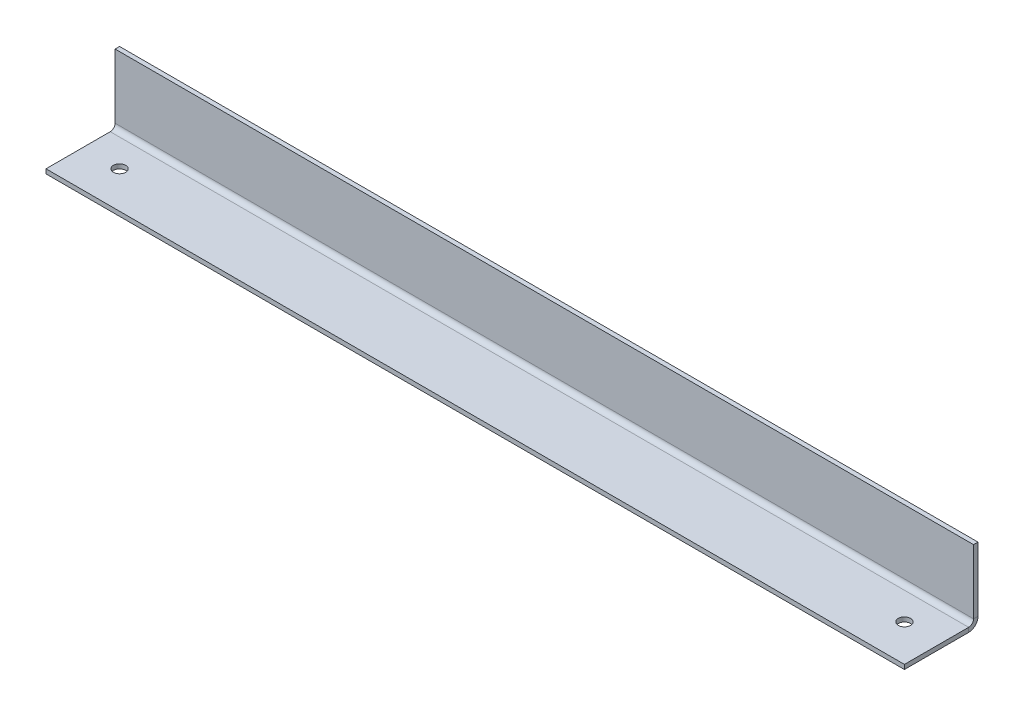
SolidWorks part; units mm, degrees
note: The reader was unsure of these and kept them because the rebuilt part matched: flange length of "Edge-Flange1".
ref_plane "Front Plane" through (0, 0, 0) normal (0, 0, 1) x (1, 0, 0)
ref_plane "Top Plane" through (0, 0, 0) normal (0, 1, 0) x (1, 0, 0)
ref_plane "Right Plane" through (0, 0, 0) normal (1, 0, 0) x (0, 0, -1)
sketch "Sketch1" plane through (0, 0, 0) normal (0, 1, 0) x (1, 0, 0)
  line L1 (0, 0) -> (444.5, 0)
  line L2 (0, 0) -> (0, 38.1)
  line L3 (0, 38.1) -> (444.5, 38.1)
  line L4 (444.5, 0) -> (444.5, 38.1)
  dimension "D1" = 444.5
  dimension "D2" = 38.1
base flange "Base-Flange1" sketch "Sketch1" thickness 2.3048 reverse thickness direction no parameters "D1"=2.54
edge flange "Edge-Flange1" sketch "Sketch8" flange angle 90 flange length 38.1 flange position material inside bend radius 2.54 thickness 2.3048 relief rectangular parameters "D6"=10
sketch "Sketch8" plane through (0, 0, -38.1) normal (0, 0, -1) x (-1, 0, 0)
  line L0 (-444.5, 0) -> (0, 0) construction
  line L1 (-444.5, 0) -> (0, 0)
  line L2 (-444.5, 0) -> (-444.5, 35.7952)
  line L3 (-444.5, 35.7952) -> (0, 35.7952)
  line L4 (0, 35.7952) -> (0, 0)
bend "EdgeBend1" bend radius 2.54 bend angle 90 parameters "D5"=1
sketch "Sketch10" plane through (0, 0, 0) normal (0, 1, 0) x (1, 0, 0)
  line L0 (0, 33.2552) -> (0, 0) construction
  line L1 (0, 0) -> (444.5, 0) construction
  line L2 (444.5, 0) -> (444.5, 33.2552) construction
  point P0 (19.05, 19.05)
  point P1 (425.45, 19.05)
  dimension "D1" = 19.05
  dimension "D2" = 19.05
  dimension "D3" = 19.05
hole_wizard "1/4 (0.25) Diameter Hole1" positions "Sketch10" profile "Sketch11" hole size "1/4" standard "ANSI Inch" end condition through all
sketch "Sketch11" plane through (19.05, 0, -19.05) normal (1, 0, 0) x (0, 0, 1)
  line L0 (0, 0) -> (0, 2.3048)
  line L1 (0, 2.3048) -> (3.175, 2.3048)
  line L2 (3.175, 2.3048) -> (3.175, 0)
  line L5 (3.175, 0) -> (0, 0)
  line L11 (0, -6.35) -> (0, 107.95) construction
  dimension "Thru Hole Dia." = 6.35
  dimension "Thru Hole Depth" = 2.3048
sketch "Bend-Lines1" [suppressed] plane through (0, 0, 0) normal (0, 1, 0) x (1, 0, 0)
sketch "Bounding-Box1" [suppressed] plane through (0, 0, 0) normal (0, 1, 0) x (1, 0, 0)
sheet metal parameters "Sheet-Metal1" thickness 2.3048 parameters "D1"=2.54
flat pattern "Flat-Pattern1" [suppressed]
sketch "Bend-Lines2" plane through (0, 0, 0) normal (0, 1, 0) x (1, 0, 0)
sketch3d "Bounding-Box2" [suppressed]
  line L0 (-444.5, 38.1, 0) -> (0, 38.1, 0) construction
  line L1 (-444.5, 0, 0) -> (0, 0, 0) construction
  line L2 (-444.5, 38.1, 0) -> (-444.5, 0, 0) construction
  line L3 (0, 38.1, 0) -> (0, 0, 0) construction
sheet metal parameters "Sheet-Metal2" thickness 2.3048 parameters "D1"=2.54
flat pattern "Flat-Pattern1"
sketch "Bend-Lines2" plane through (0, 0, 0) normal (0, 1, 0) x (1, 0, 0)
  line L0 (444.5, 36.1552) -> (0, 36.1552) construction
  line L1 (444.5, 36.1552) -> (0, 36.1552) construction
sketch3d "Bounding-Box2" [suppressed]
  line L0 (444.5, 72.3104, 0) -> (0, 72.3104, 0) construction
  line L1 (444.5, 0, 0) -> (0, 0, 0) construction
  line L2 (444.5, 72.3104, 0) -> (444.5, 0, 0) construction
  line L3 (0, 72.3104, 0) -> (0, 0, 0) construction
bend of the flat pattern "Flatten-<EdgeBend1>1"
sheet metal parameters "Sheet-Metal3" thickness 2.3048 parameters "D1"=2.54
flat pattern "Flat-Pattern1"
sketch "Bend-Lines2" plane through (0, 0, 0) normal (0, 1, 0) x (1, 0, 0)
  line L0 (444.5, 36.1552) -> (0, 36.1552) construction
  line L1 (444.5, 36.1552) -> (0, 36.1552) construction
sketch3d "Bounding-Box2" [suppressed]
  line L0 (444.5, 72.3104, 0) -> (0, 72.3104, 0) construction
  line L1 (444.5, 0, 0) -> (0, 0, 0) construction
  line L2 (444.5, 72.3104, 0) -> (444.5, 0, 0) construction
  line L3 (0, 72.3104, 0) -> (0, 0, 0) construction
bend of the flat pattern "Flatten-<EdgeBend1>1"
